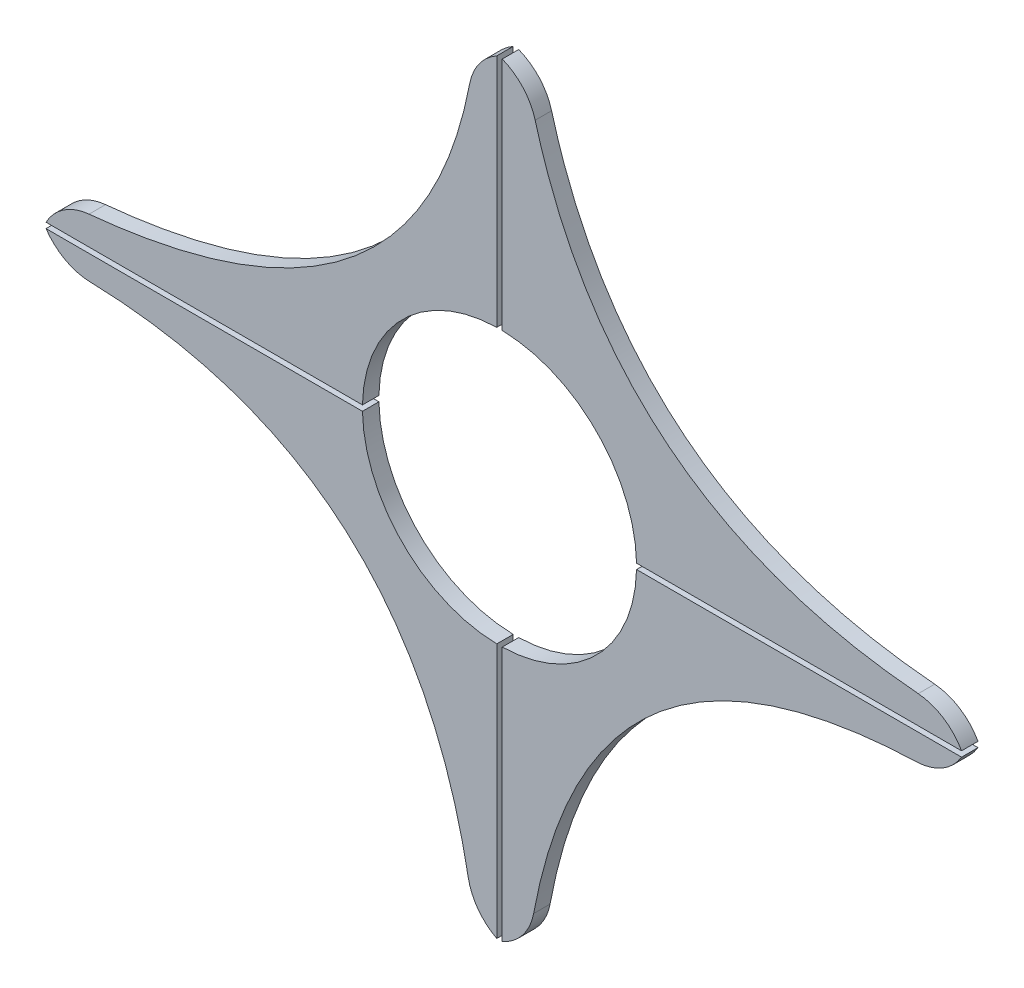
SolidWorks part; units mm, degrees
ref_plane "Plano frontal" through (0, 0, 0) normal (0, 0, 1) x (1, 0, 0)
ref_plane "Plano superior" through (0, 0, 0) normal (0, 1, 0) x (1, 0, 0)
ref_plane "Plano direito" through (0, 0, 0) normal (1, 0, 0) x (0, 0, -1)
sketch "Esboço2" plane through (0, 0, 0) normal (0, 0, 1) x (1, 0, 0)
  line L1 (-82.7093, 67.884) -> (84.2698, 67.884)
  line L2 (-82.7093, 67.884) -> (-82.7093, -71.5253)
  line L3 (-82.7093, -71.5253) -> (84.2698, -71.5253)
  line L4 (84.2698, 67.884) -> (84.2698, -71.5253)
extrude "Ressalto-extrusão1" add sketch "Esboço2" along normal blind 3 contours L2 L1 L4 L3
sketch "Esboço3" plane through (0, 0, 3) normal (0, 0, 1) x (1, 0, 0)
  circle A0 centre (0, 0) radius 25
extrude "Corte-extrusão1" cut sketch "Esboço3" against normal blind 3
sketch "Esboço4" plane through (0, 0, 3) normal (0, 0, 1) x (1, 0, 0)
  line L1 (84.2698, 67.884) -> (84.2698, -71.5253) construction
  line L2 (84.2698, 0) -> (84.2698, 0.5)
  line L3 (84.2698, 0.5) -> (24.995, 0.5)
  line L4 (24.995, 0.5) -> (25, 0)
  line L5 (25, 0) -> (-25, 0)
  line L7 (25, 0) -> (24.995, -0.5)
  line L8 (-25, 0) -> (25, 0)
  line L9 (24.995, -0.5) -> (84.2698, -0.5)
  line L10 (84.2698, -0.5) -> (84.2698, 0)
  circle A1 centre (0, 0) radius 25 construction
  dimension "D1" = 0.5
  dimension "D2" = 50
  dimension "D3" = 0.5
extrude "Corte-extrusão2" cut sketch "Esboço4" against normal blind 3 contours L7 L9 L10 L2 L3 L4
sketch "Esboço5" plane through (0, 0, 3) normal (0, 0, 1) x (1, 0, 0)
  line L1 (0, 0) -> (0.5, 0)
  line L2 (0.5, 0) -> (0.5, 86.7775)
  line L3 (-0.5, 0) -> (-0.5, 86.7825)
  line L4 (-0.5, 86.7825) -> (0.5, 86.7775)
  line L5 (-0.5, 0) -> (0, 0)
  point P1 (0, 0)
  dimension "D1" = 0.5
  dimension "D2" = 0.5
extrude "Corte-extrusão3" cut sketch "Esboço5" against normal blind 3
sketch "Esboço6" plane through (0, 0, 0) normal (0, 0, -1) x (-1, 0, 0)
  line L1 (89.2448, 0) -> (89.2448, 0.5)
  line L2 (89.2448, 0.5) -> (0, 0.5)
  line L3 (0, 0.5) -> (0, 0)
  line L4 (0, 0) -> (0, -0.5)
  line L5 (0, -0.5) -> (89.2448, -0.5)
  line L6 (89.2448, -0.5) -> (89.2448, 0)
  dimension "D1" = 0.5
  dimension "D2" = 0.5
extrude "Corte-extrusão4" cut sketch "Esboço6" against normal blind 3 contours L3 L4 L5 L6 L1 L2
sketch "Esboço7" plane through (0, 0, 0) normal (0, 0, -1) x (-1, 0, 0)
  line L1 (0, -80.8885) -> (0.5, -80.8885)
  line L2 (0.5, -80.8885) -> (0.5, 0)
  line L3 (0.5, 0) -> (0, 0)
  line L4 (0, 0) -> (-0.5, 0)
  line L5 (-0.5, 0) -> (-0.5, -80.8885)
  line L6 (-0.5, -80.8885) -> (0, -80.8885)
  dimension "D1" = 0.5
  dimension "D2" = 0.5
extrude "Corte-extrusão5" cut sketch "Esboço7" against normal blind 3
sketch "Esboço8" plane through (0, 0, 0) normal (0, 0, -1) x (-1, 0, 0)
  line L0 (82.7093, 67.884) -> (0.5, 67.884) construction
  line L1 (82.7093, 67.884) -> (82.7093, 0.5) construction
  line L2 (4.3879, 67.884) -> (82.7093, 67.884)
  line L3 (82.7093, 67.884) -> (82.7093, 5.1602)
  spline S0 degree 2 poles (4.3879, 67.884) (11.3012, 8.4425) (82.7093, 5.1602) knots 0 0 0 1 1 1
extrude "Corte-extrusão6" cut sketch "Esboço8" against normal blind 3
sketch "Esboço9" plane through (0, 0, 0) normal (0, 0, -1) x (-1, 0, 0)
  line L0 (82.7093, -0.5) -> (82.7093, -71.5253) construction
  line L1 (82.7093, -71.5253) -> (0.5, -71.5253) construction
  line L2 (4.5897, -71.5253) -> (82.7093, -71.5253)
  line L3 (82.7093, -71.5253) -> (82.7093, -4.9281)
  spline S0 degree 2 poles (82.7093, -4.9281) (13.5471, -2.5785) (4.5897, -71.5253) knots 0 0 0 1 1 1
extrude "Corte-extrusão7" cut sketch "Esboço9" against normal blind 3
sketch "Esboço10" plane through (0, 0, 0) normal (0, 0, -1) x (-1, 0, 0)
  line L0 (-0.5, 67.884) -> (-84.2698, 67.884) construction
  line L1 (-84.2698, 67.884) -> (-84.2698, 0.5) construction
  line L2 (-84.2698, 5.1602) -> (-84.2698, 67.884)
  line L3 (-84.2698, 67.884) -> (-4.8933, 67.884)
  spline S0 degree 2 poles (-4.8933, 67.884) (-17.7213, 6.8219) (-84.2698, 5.1602) knots 0 0 0 1 1 1
extrude "Corte-extrusão8" cut sketch "Esboço10" against normal blind 3
sketch "Esboço11" plane through (0, 0, 0) normal (0, 0, -1) x (-1, 0, 0)
  line L0 (-84.2698, -0.5) -> (-84.2698, -71.5253) construction
  line L1 (-0.5, -71.5253) -> (-84.2698, -71.5253) construction
  line L2 (-84.2698, -71.5253) -> (-84.2698, -5.3316)
  line L3 (-84.2698, -71.5253) -> (-5.0951, -71.5253)
  spline S0 degree 2 poles (-84.2698, -5.3316) (-13.6113, -3.379) (-5.0951, -71.5253) knots 0 0 0 1 1 1
extrude "Corte-extrusão9" cut sketch "Esboço11" against normal blind 3
fillet "Filete1" radius 10 1 edges at (4.8933, 67.884, 1.5)
fillet "Filete2" radius 10 1 edges at (-4.3879, 67.884, 1.5)
fillet "Filete3" radius 10 1 edges at (-82.7093, 5.1602, 1.5)
fillet "Filete4" radius 10 1 edges at (-82.7093, -4.9281, 1.5)
fillet "Filete5" radius 10 1 edges at (-4.5897, -71.5253, 1.5)
fillet "Filete6" radius 10 1 edges at (5.0951, -71.5253, 1.5)
fillet "Filete7" radius 10 1 edges at (84.2698, 5.1602, 1.5)
fillet "Filete8" radius 10 1 edges at (84.2698, -5.3316, 1.5)
